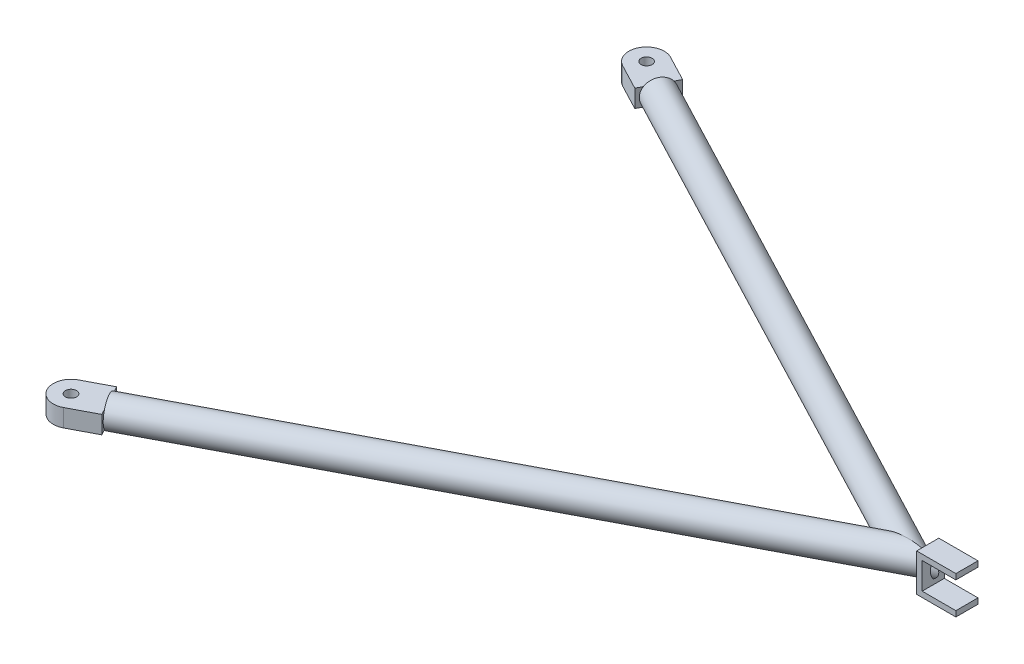
SolidWorks part; units mm, degrees
ref_plane "Front Plane" through (0, 0, 0) normal (0, 0, 1) x (1, 0, 0)
ref_plane "Top Plane" through (0, 0, 0) normal (0, 1, 0) x (1, 0, 0)
ref_plane "Right Plane" through (0, 0, 0) normal (1, 0, 0) x (0, 0, -1)
sketch "Sketch1" plane through (0, 0, 0) normal (0, 1, 0) x (1, 0, 0)
  line L0 (-314.9498, -165.1) -> (0, 0)
  line L1 (0, 0) -> (-314.9498, 165.1)
  line L2 (-314.9498, 165.1) -> (-314.9498, -165.1) construction
  dimension "D1" = 355.6
  dimension "D2" = 355.6
  dimension "D3" = 330.2
ref_plane "Plane1" through (-314.9498, 0, 165.1) normal (0.8857, 0, -0.4643) x (-0.4643, 0, -0.8857)
sketch "Sketch2" plane through (-314.9498, 0, 165.1) normal (0.8857, 0, -0.4643) x (-0.4643, 0, -0.8857)
  circle A0 centre (0, 0) radius 8.255
  dimension "D1" = 16.51
sweep "Sweep1" add profiles "Sketch2" path "Sketch1"
sketch "Sketch3" plane through (0, 0, 0) normal (0, 0, 1) x (1, 0, 0)
  line L0 (33.9318, 10.795) -> (11.43, 10.795)
  line L1 (11.43, 10.795) -> (11.43, -10.795)
  line L2 (11.43, -10.795) -> (33.9318, -10.795)
  line L3 (33.9318, -10.795) -> (33.9318, -7.62)
  line L4 (33.9318, -7.62) -> (14.605, -7.62)
  line L5 (14.605, -7.62) -> (14.605, 7.62)
  line L6 (14.605, 7.62) -> (33.9318, 7.62)
  line L7 (33.9318, 7.62) -> (33.9318, 10.795)
  line L8 (17.78, 0) -> (-17.78, 0) construction
  ellipse E0 centre (0, 0) end of major axis (17.78, 0) minor radius 8.255 construction
  ellipse E1 centre (0, 0) end of major axis (17.78, 0) minor radius 8.255 construction
  point P21 (11.43, 0)
  dimension "D1" = 3.175
  dimension "D2" = 15.24
  dimension "D3" = 3.175
  dimension "D4" = 6.35
extrude "Boss-Extrude1" add sketch "Sketch3" along normal blind 6.35 and the other way blind 6.35
sketch "Sketch4" plane through (-314.9498, 0, 165.1) normal (-0.8857, 0, 0.4643) x (0.4643, 0, 0.8857)
  line L1 (-10.16, 5.08) -> (10.16, 5.08)
  line L2 (-10.16, 5.08) -> (-10.16, -5.08)
  line L3 (-10.16, -5.08) -> (10.16, -5.08)
  line L4 (10.16, 5.08) -> (10.16, -5.08)
  line L5 (-10.16, 5.08) -> (10.16, -5.08) construction
  line L6 (-10.16, -5.08) -> (10.16, 5.08) construction
  circle A1 centre (0, 0) radius 8.255
  circle A2 centre (0, 0) radius 8.255 construction
  dimension "D2" = 20.32
  dimension "D3" = 10.16
  dimension "D1" = 0
extrude "Boss-Extrude2" add sketch "Sketch4" along normal blind 10.16 and the other way blind 16.256
sketch "Sketch5" plane through (-314.9498, 0, -165.1) normal (-0.8857, 0, -0.4643) x (-0.4643, 0, 0.8857)
  line L1 (-10.16, 5.08) -> (10.16, 5.08)
  line L2 (-10.16, 5.08) -> (-10.16, -5.08)
  line L3 (-10.16, -5.08) -> (10.16, -5.08)
  line L4 (10.16, 5.08) -> (10.16, -5.08)
  line L5 (-10.16, 5.08) -> (10.16, -5.08) construction
  line L6 (-10.16, -5.08) -> (10.16, 5.08) construction
  point P0 (0, 0)
  dimension "D1" = 20.32
  dimension "D2" = 10.16
extrude "Boss-Extrude3" add sketch "Sketch5" along normal blind 10.16 and the other way blind 16.51
sketch "Sketch6" plane through (0, 5.08, 0) normal (0, 1, 0) x (1, 0, 0)
  line L0 (-295.6099, 166.4332) -> (-319.2312, 178.8157) construction
  line L1 (-305.0442, 148.4361) -> (-328.6655, 160.8186) construction
  line L2 (-328.6655, 160.8186) -> (-319.2312, 178.8157) construction
  line L3 (-319.6669, 156.1014) -> (-328.6655, 160.8186)
  line L4 (-328.6655, 160.8186) -> (-323.9483, 169.8171)
  arc A0 (-323.9483, 169.8171) -> (-319.6669, 156.1014) centre (-314.9498, 165.1) ccw
extrude "Cut-Extrude1" cut sketch "Sketch6" against normal through all
ref_plane "Plane2" through (0, 0, 0) normal (-0.4643, 0, 0.8857) x (0.8857, 0, 0.4643)
ref_plane "Plane3" through (0, 0, 0) normal (0.4643, 0, 0.8857) x (0.8857, 0, -0.4643)
mirror "Mirror1" about plane through (0, 0, 0) normal (-0.4643, 0, 0.8857) of "Cut-Extrude1"
sketch "Sketch7" plane through (0, 5.08, 0) normal (0, 1, 0) x (1, 0, 0)
  line L0 (-295.8349, -166.5511) -> (-319.2312, -178.8157) construction
  line L1 (-305.2692, -148.554) -> (-328.6655, -160.8186) construction
  line L2 (-319.2312, -178.8157) -> (-328.6655, -160.8186) construction
  line L3 (-310.2326, -174.0986) -> (-319.2312, -178.8157)
  line L4 (-319.2312, -178.8157) -> (-323.9483, -169.8171)
  arc A0 (-310.2326, -174.0986) -> (-323.9483, -169.8171) centre (-314.9498, -165.1) cw
extrude "Cut-Extrude2" cut sketch "Sketch7" against normal through all
mirror "Mirror2" about plane through (0, 0, 0) normal (0.4643, 0, 0.8857) of "Cut-Extrude2"
sketch "Sketch8" plane through (-314.9498, 0, 165.1) normal (-0.8857, 0, 0.4643) x (0.4643, 0, 0.8857)
  line L0 (6.5068, -5.08) -> (-6.5068, -5.08) construction
  line L1 (-6.5068, 5.08) -> (6.5068, 5.08) construction
  line L2 (6.5068, -5.08) -> (-6.5068, -5.08)
  line L3 (-6.5068, 5.08) -> (6.5068, 5.08)
  arc A0 (-6.5068, -5.08) -> (6.5068, -5.08) centre (0, 0) ccw construction
  arc A1 (6.5068, 5.08) -> (-6.5068, 5.08) centre (0, 0) ccw construction
  arc A2 (-6.5068, -5.08) -> (6.5068, -5.08) centre (0, 0) ccw
  arc A3 (6.5068, 5.08) -> (-6.5068, 5.08) centre (0, 0) ccw
extrude "Cut-Extrude3" cut sketch "Sketch8" against normal up to surface (16.256 mm away) up to face at (-296.4801, 0, 165.3204)
sketch "Sketch9" plane through (-314.9498, 0, -165.1) normal (-0.8857, 0, -0.4643) x (-0.4643, 0, 0.8857)
  line L0 (6.5068, -5.08) -> (-6.5068, -5.08) construction
  line L1 (-6.5068, 5.08) -> (6.5068, 5.08) construction
  line L2 (6.5068, -5.08) -> (-6.5068, -5.08)
  line L3 (-6.5068, 5.08) -> (6.5068, 5.08)
  arc A0 (-6.5068, -5.08) -> (6.5068, -5.08) centre (0, 0) ccw construction
  arc A1 (6.5068, 5.08) -> (-6.5068, 5.08) centre (0, 0) ccw construction
  arc A2 (-6.5068, -5.08) -> (6.5068, -5.08) centre (0, 0) ccw
  arc A3 (6.5068, 5.08) -> (-6.5068, 5.08) centre (0, 0) ccw
extrude "Cut-Extrude4" cut sketch "Sketch9" against normal up to surface (16.51 mm away) up to face at (-304.3991, 0, -149.6668)
sketch "Sketch10" plane through (0, 5.08, 0) normal (0, 1, 0) x (1, 0, 0)
  point P0 (-314.9498, 165.1)
  point P1 (-314.9498, -165.1)
hole_wizard "E (0.25) Diameter Hole1" positions "3DSketch1" profile "Sketch11" hole size "E" standard "ANSI Inch"
sketch3d "3DSketch1"
  point P0 (-314.9498, 5.08, -165.1)
  point P3 (-314.9498, 5.08, 165.1)
sketch "Sketch11" plane through (-314.9498, 5.08, -165.1) normal (1, 0, 0) x (0, 0, 1)
  line L0 (0, 0) -> (0, 20.9577)
  line L1 (0, 20.9577) -> (3.175, 19.05)
  line L2 (3.175, 19.05) -> (3.175, 0)
  line L5 (3.175, 0) -> (0, 0)
  line L10 (0, 20.9577) -> (-3.175, 19.05) construction
  line L11 (0, -6.35) -> (0, 107.95) construction
  dimension "Hole Dia." = 6.35
  dimension "Hole Depth" = 19.05
  dimension "Drill Angle" = 118
